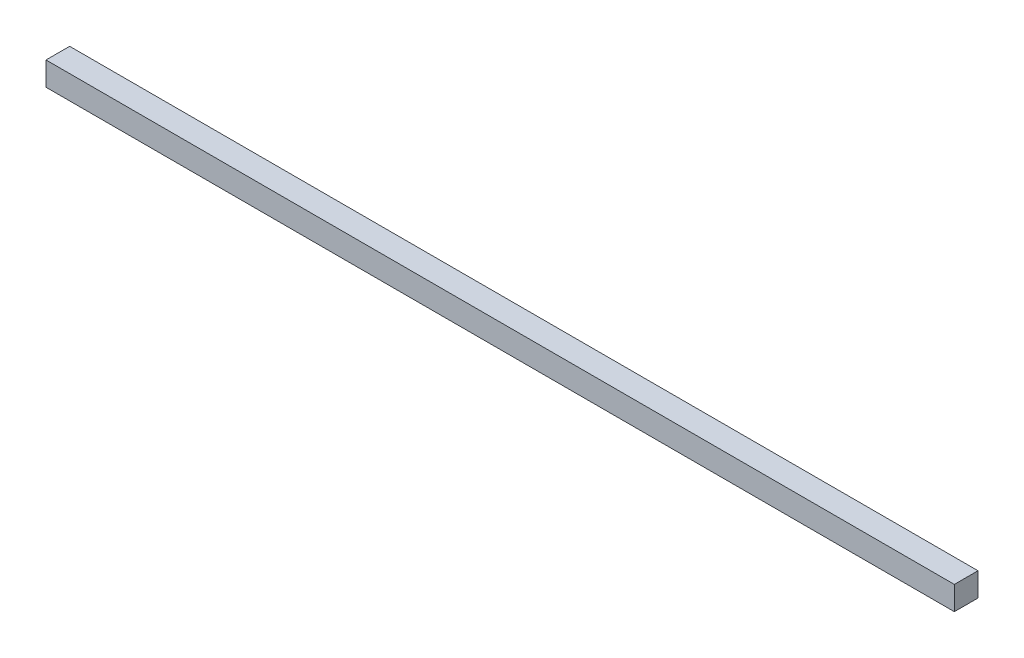
SolidWorks part; units mm, degrees
material "Plain Carbon Steel"
ref_plane "Front Plane" through (0, 0, 0) normal (0, 0, 1) x (1, 0, 0)
ref_plane "Top Plane" through (0, 0, 0) normal (0, 1, 0) x (1, 0, 0)
ref_plane "Right Plane" through (0, 0, 0) normal (1, 0, 0) x (0, 0, -1)
sketch "Sketch1" plane through (0, 0, 0) normal (0, 0, 1) x (1, 0, 0)
  line L0 (-192, -5) -> (192, -5)
  line L1 (192, -5) -> (192, 5)
  line L2 (192, 5) -> (-192, 5)
  line L3 (-192, 5) -> (-192, -5)
extrude "Boss-Extrude1" add sketch "Sketch1" along normal mid plane 10
